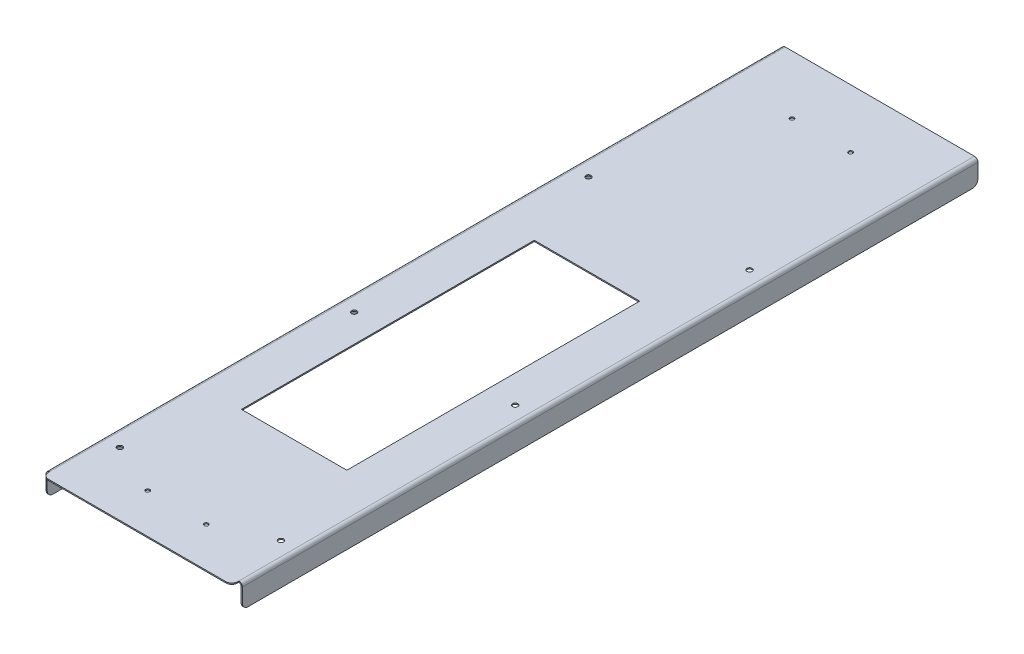
SolidWorks part; units mm, degrees
note: The reader was unsure of these and kept them because the rebuilt part matched: thickness of "Базовая кромка1", "Ребро-кромка1", "Листовой металл3", "Листовой металл4"; flange length of "Ребро-кромка1".
material "AISI 304"
ref_plane "Спереди" through (0, 0, 0) normal (0, 0, 1) x (1, 0, 0)
ref_plane "Сверху" through (0, 0, 0) normal (0, 1, 0) x (1, 0, 0)
ref_plane "Справа" through (0, 0, 0) normal (1, 0, 0) x (0, 0, -1)
sketch "Эскиз1" plane through (0, 0, 0) normal (0, 1, 0) x (1, 0, 0)
  line L0 (0, 134) -> (0, -366) construction
  line L1 (-161.5, 634) -> (161.5, 634)
  line L2 (-161.5, 634) -> (-161.5, -634)
  line L3 (-161.5, -634) -> (161.5, -634)
  line L4 (161.5, 634) -> (161.5, -634)
  line L5 (-161.5, 634) -> (161.5, -634) construction
  line L6 (-161.5, -634) -> (161.5, 634) construction
  line L9 (-90, 134) -> (90, 134)
  line L10 (-90, 134) -> (-90, -366)
  line L12 (-90, -366) -> (90, -366)
  line L13 (90, 134) -> (90, -366)
  line L14 (-137.5, -634) -> (-137.5, 634) construction
  line L15 (137.5, 634) -> (137.5, -634) construction
  line L16 (-137.5, 0) -> (137.5, 0) construction
  line L17 (50, 534) -> (-50, 534) construction
  line L18 (0, 534) -> (0, 0) construction
  line L19 (0, 0) -> (0, -566) construction
  line L20 (50, -566) -> (-50, -566) construction
  circle A1 centre (-137.5, -526) radius 4.5
  circle A2 centre (137.5, -526) radius 4.5
  circle A3 centre (-137.5, -126) radius 4.5
  circle A4 centre (137.5, -126) radius 4.5
  circle A5 centre (-137.5, 274) radius 4.5
  circle A6 centre (137.5, 274) radius 4.5
  circle A14 centre (-50, -566) radius 3.5
  circle A15 centre (50, -566) radius 3.5
  circle A17 centre (-50, 534) radius 3.5
  circle A18 centre (50, 534) radius 3.5
  dimension "D6" = 275
  dimension "D7" = 9
  dimension "D11" = 7
  dimension "D1" = 268
  dimension "D2" = 323
  dimension "D3" = 180
  dimension "D4" = 500
  dimension "D5" = 500
  dimension "D8" = 108
  dimension "D10" = 400
  dimension "D12" = 100
  dimension "D13" = 200
  dimension "D14" = 400
  dimension "D9" = 3
base flange "Базовая кромка1" sketch "Эскиз1" thickness 2 reverse thickness direction no parameters "D1"=4
edge flange "Ребро-кромка1" sketch "Эскиз10" flange profiles "Эскиз10", "Эскиз11" flange angle 90 flange length 40 flange position bend outside bend radius 4 thickness 2 relief rectangular parameters "D6"=10, "D8"=1
sketch "Эскиз10" plane through (161.5, -2, 0) normal (1, 0, 0) x (0, 0, 1)
  line L2 (-634, 0) -> (-634, 38)
  line L3 (-634, 38) -> (622, 38)
  line L4 (622, 38) -> (622, 0)
  line L5 (634, 0) -> (634, -2) construction
  line L7 (634, 0) -> (-634, 0) construction
  line L8 (622, 0) -> (-634, 0)
  dimension "D1" = 12
sketch "Эскиз11" plane through (-161.5, -2, 0) normal (-1, 0, 0) x (0, 0, -1)
  line L0 (-634, 0) -> (-634, -2) construction
  line L2 (-622, 0) -> (-622, 38)
  line L3 (-622, 38) -> (634, 38)
  line L4 (634, 38) -> (634, 0)
  line L7 (634, 0) -> (-634, 0) construction
  line L8 (634, 0) -> (-622, 0)
  dimension "D1" = 12
bend "EdgeBend1" bend radius 4 bend angle 90 parameters "D5"=1
bend "EdgeBend2" bend radius 4 bend angle 90 parameters "D5"=2
fillet "Скругление1" radius 10 4 edges at (-166.5, -40, 622) (166.5, -40, 622) (166.5, -40, -634) (-166.5, -40, -634)
fillet "Скругление2" radius 10 2 edges at (161.5, -1, 634) (-161.5, -1, 634)
sketch "Сгиб-Линии1" plane through (0, 0, 0) normal (0, 1, 0) x (1, 0, 0)
sketch "Граничная рамка1" plane through (0, 0, 0) normal (0, 1, 0) x (1, 0, 0)
sheet metal parameters "Листовой металл3" thickness 2 parameters "D1"=4
flat pattern "Развертка3" [suppressed]
sketch "Сгиб-Линии2" plane through (0, 0, 0) normal (0, 1, 0) x (1, 0, 0)
sketch "Граничная рамка2" [suppressed] plane through (0, 0, 0) normal (0, 1, 0) x (1, 0, 0)
sheet metal parameters "Листовой металл4" thickness 2 parameters "D1"=4, "D7"=4
flat pattern "Развертка3" [suppressed]
sketch "Сгиб-Линии2" plane through (0, 0, 0) normal (0, 1, 0) x (1, 0, 0)
sketch "Граничная рамка2" [suppressed] plane through (0, 0, 0) normal (0, 1, 0) x (1, 0, 0)
bend of the flat pattern "Плоское состояние-<EdgeBend1>1"
bend of the flat pattern "Плоское состояние-<EdgeBend2>1"
